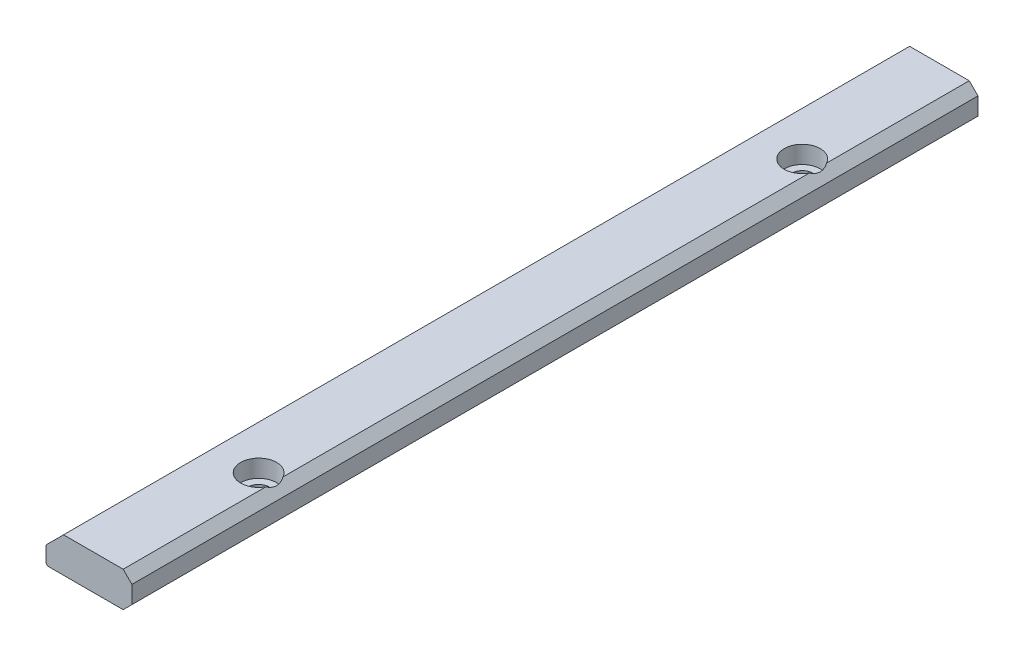
SolidWorks part; units mm, degrees
ref_plane "前视基准面" through (0, 0, 0) normal (0, 0, 1) x (1, 0, 0)
ref_plane "上视基准面" through (0, 0, 0) normal (0, 1, 0) x (1, 0, 0)
ref_plane "右视基准面" through (0, 0, 0) normal (1, 0, 0) x (0, 0, -1)
sketch "草图1" plane through (0, 0, 0) normal (0, 0, 1) x (1, 0, 0)
  line L1 (0, 0) -> (8, 0)
  line L3 (0, 4) -> (8, 4)
  line L4 (8, 0) -> (8, 4)
  line L5 (0, 4) -> (-1.8, 4)
  line L6 (0, 0) -> (0, -1.9)
  line L7 (0, -1.9) -> (-1.8, -1.9)
  line L8 (-1.8, 4) -> (-1.8, -1.9)
  dimension "D1" = 1.8
  dimension "D2" = 1.9
  dimension "D3" = 4
  dimension "D4" = 8
extrude "凸台-拉伸1" add sketch "草图1" against normal blind 96.5
chamfer "倒角1" distance 1 angle 45 1 edges at (8, 0, -48.25)
chamfer "倒角2" distance 1 angle 45 1 edges at (8, 4, -48.25)
sketch "草图2" plane through (0, 4, 0) normal (0, 1, 0) x (1, 0, 0)
  line L0 (5.2, 105.0677) -> (5.2, -16.3861) construction
  line L1 (-1.8, 96.5) -> (-1.8, 0) construction
  line L4 (-28.4042, 48.25) -> (44.7588, 48.25) construction
  line L9 (-1.8, 0) -> (7, 0)
  line L10 (7, 0) -> (7, 96.5)
  line L11 (7, 96.5) -> (-1.8, 96.5)
  line L12 (-1.8, 96.5) -> (-1.8, 0)
  line L13 (-1.8, 0) -> (7, 0) construction
  line L15 (7, 96.5) -> (-1.8, 96.5) construction
  circle A1 centre (5.2, 79.25) radius 2.05
  circle A3 centre (5.2, 17.25) radius 2.05
  circle A4 centre (5.2, 79.25) radius 1.2
  circle A7 centre (5.2, 17.25) radius 1.2
  dimension "D3" = 62
  dimension "D5" = 4.1
  dimension "D6" = 2.4
  dimension "D1" = 0
  dimension "D2" = 7
extrude "切除-拉伸1" cut sketch "草图2" against normal blind 10 and the other way through all contours A7 | A4
extrude "切除-拉伸2" cut sketch "草图2<3>" against normal blind 2 contours A1 | A3
sketch "草图2<3>" plane through (0, 4, 0) normal (0, 1, 0) x (1, 0, 0) same geometry as "草图2"
chamfer "倒角3" distance 2 angle 45 1 edges at (-1.8, 4, -48.25)
sketch "草图3" plane through (0, -1.9, 0) normal (0, -1, 0) x (1, 0, 0)
  line L0 (0, -96.5) -> (0, 0) construction
  line L1 (-1.8, -96.5) -> (0, -96.5)
  line L2 (-1.8, -96.5) -> (-1.8, -89.1)
  line L3 (-1.8, -89.1) -> (0, -89.1)
  line L4 (0, -96.5) -> (0, -89.1)
  line L5 (-1.8, 0) -> (0, 0)
  line L6 (-1.8, 0) -> (-1.8, -7.4)
  line L7 (-1.8, -7.4) -> (0, -7.4)
  line L8 (0, 0) -> (0, -7.4)
  dimension "D1" = 7.4
extrude "切除-拉伸3" cut sketch "草图3" against normal up to surface (1.9 mm away) up to face at (5.2, 0, -18.45)
chamfer "倒角4" distance 0.2 angle 45 8 edges at (0, -0.95, -89.1) (0, -0.95, -7.4) (0, -1.9, -48.25) (-1.8, 0, -92.8) (-1.8, -0.95, -89.1) (-1.8, 0, -3.7) (-1.8, -0.95, -7.4) (-1.8, -1.9, -48.25)
chamfer "倒角5" distance 0.6 angle 45 2 edges at (-0.9, -1.9, -89.1) (-0.9, -1.9, -7.4)
